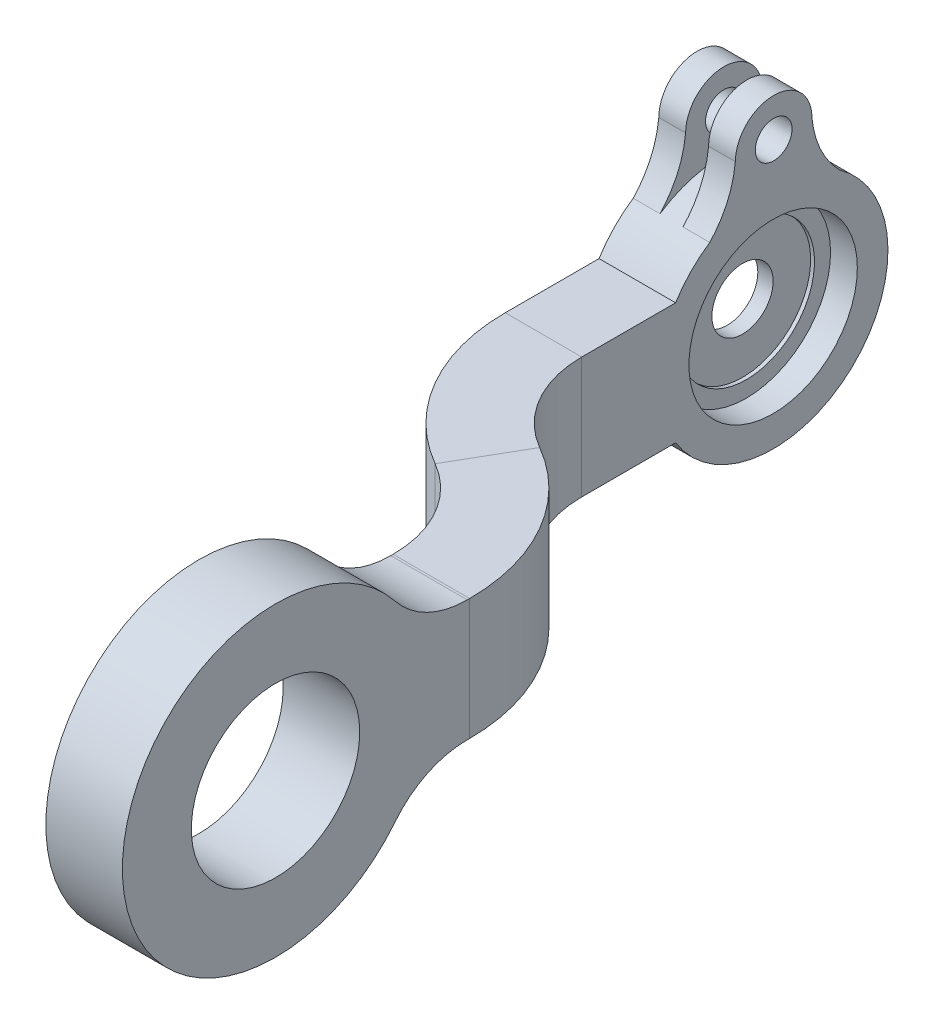
SolidWorks part; units mm, degrees
material "Resina de melamina"
ref_plane "Alzado" through (0, 0, 0) normal (0, 0, 1) x (1, 0, 0)
ref_plane "Planta" through (0, 0, 0) normal (0, 1, 0) x (1, 0, 0)
ref_plane "Vista lateral" through (0, 0, 0) normal (1, 0, 0) x (0, 0, -1)
sketch "Croquis1" plane through (0, 0, 0) normal (0, 1, 0) x (1, 0, 0)
  line L0 (0, 0) -> (0, 60) construction
  line L1 (0, 60) -> (-20, 60) construction
  line L2 (-20, 60) -> (-20, 85) construction
  line L3 (0, 15) -> (-20, 25.359) construction
  line L4 (-20, 85) -> (-20, 60)
  line L5 (0, 25.359) -> (0, 0)
  arc A0 (-20, 60) -> (-10, 42.6795) centre (0, 60) ccw
  arc A1 (0, 25.359) -> (-10, 42.6795) centre (-20, 25.359) ccw
  dimension "D4" = 20
  dimension "D1" = 60
  dimension "D2" = 25
  dimension "D3" = 20
sketch "Croquis2" plane through (0, 0, 0) normal (0, 0, 1) x (1, 0, 0)
  line L1 (5, -7.9175) -> (-5, -7.9175)
  line L2 (5, -7.9175) -> (5, 7.9175)
  line L3 (5, 7.9175) -> (-5, 7.9175)
  line L4 (-5, -7.9175) -> (-5, 7.9175)
  line L5 (5, -7.9175) -> (-5, 7.9175) construction
  line L6 (5, 7.9175) -> (-5, -7.9175) construction
  point P0 (0, 0)
  dimension "D1" = 10
sweep "Barrer1" add profiles "Croquis2" path "Croquis1"
sketch "Croquis4" plane through (-15, 0, 0) normal (1, 0, 0) x (0, 0, -1)
  line L1 (85, -7.9175) -> (85, 7.9175) construction
  circle A0 centre (85, 0) radius 15
  dimension "D2" = 30
extrude "Saliente-Extruir1" add sketch "Croquis4" against normal blind 10
sketch "Croquis5" plane through (5, 0, 0) normal (1, 0, 0) x (0, 0, -1)
  circle A0 centre (0, 0) radius 20
  dimension "D1" = 40
extrude "Saliente-Extruir2" add sketch "Croquis5" against normal blind 10
sketch "Croquis6" plane through (-15, 0, 0) normal (1, 0, 0) x (0, 0, -1)
  line L0 (60, 0) -> (85, 0) construction
  circle A0 centre (85, 0) radius 4
  dimension "D1" = 8
sketch "Croquis7" plane through (5, 0, 0) normal (1, 0, 0) x (0, 0, -1)
  circle A0 centre (0, 0) radius 11
  dimension "D1" = 22
ref_plane "Plano1" through (-15, 0, 0) normal (1, 0, 0) x (0, 0, -1)
sketch "Croquis12" plane through (-15, 0, 0) normal (1, 0, 0) x (0, 0, -1)
  line L0 (85.0685, -0.0274) -> (85.0685, 24.9726) construction
  line L1 (85.0685, 24.9726) -> (85.0685, 19.9726) construction
  line L2 (85.0685, 24.9726) -> (85.0685, 14.9726) construction
  arc A0 (90.0685, 19.9726) -> (80.0685, 19.9726) centre (85.0685, 19.9726) ccw
  arc A1 (94.2885, 11.6439) -> (75.8485, 11.6439) centre (85.0685, -0.0274) ccw
  spline S0 degree 2 poles (80.0685, 19.9726) (79.5667, 15.0283) (75.8485, 11.6439) knots 0 0 0 1 1 1
  spline S1 degree 2 poles (90.0685, 19.9726) (90.5703, 15.0283) (94.2885, 11.6439) knots 0 0 0 1 1 1
  dimension "D1" = 25
  dimension "D2" = 5
extrude "Saliente-Extruir5" add sketch "Croquis12" against normal blind 3.5
ref_plane "Plano2" through (-20, 0, 0) normal (1, 0, 0) x (0, 0, -1)
mirror "Simetría1" about plane through (-20, 0, 0) normal (1, 0, 0) of "Saliente-Extruir5"
sketch "Croquis13" plane through (-15, 0, 0) normal (1, 0, 0) x (0, 0, -1)
  circle A0 centre (85.0685, 19.9726) radius 2.4
  dimension "D1" = 4.8
extrude "Cortar-Extruir1" cut sketch "Croquis13" against normal blind 10
extrude "Cortar-Extruir3" cut sketch "Croquis7" against normal blind 10
fillet "Redondeo2" radius 12 1 edges at (0, 7.9175, -18.3661) type face fillet first side face at (0, 7.9175, -21.8625) second side face at (0, 0, 0.8169)
fillet "Redondeo3" radius 12 1 edges at (0, -7.9175, -18.3661) type face fillet first side face at (0, -7.9175, -21.8625) second side face at (0, -0.1875, 1.4075)
sketch "Croquis14" plane through (-25, 0, 0) normal (-1, 0, 0) x (0, 0, 1)
  circle A0 centre (-85, 0) radius 11
  dimension "D1" = 22
extrude "Cortar-Extruir4" cut sketch "Croquis14" against normal blind 4
extrude "Cortar-Extruir5" cut sketch "Croquis6" against normal blind 6 contours A0
sketch "Croquis15" plane through (-15, 0, 0) normal (1, 0, 0) x (0, 0, -1)
  circle A0 centre (85, 0) radius 11
  dimension "D1" = 22
extrude "Cortar-Extruir6" cut sketch "Croquis15" against normal blind 4
sketch "Croquis16" plane through (-21, 0, 0) normal (-1, 0, 0) x (0, 0, 1)
  circle A0 centre (-85, 0) radius 8.9
  circle A1 centre (-85, 0) radius 11
  dimension "D1" = 17.8
extrude "Saliente-Extruir6" add sketch "Croquis16" along normal blind 0.5
mirror "Simetría2" about plane through (-20, 0, 0) normal (1, 0, 0) of "Saliente-Extruir6"
